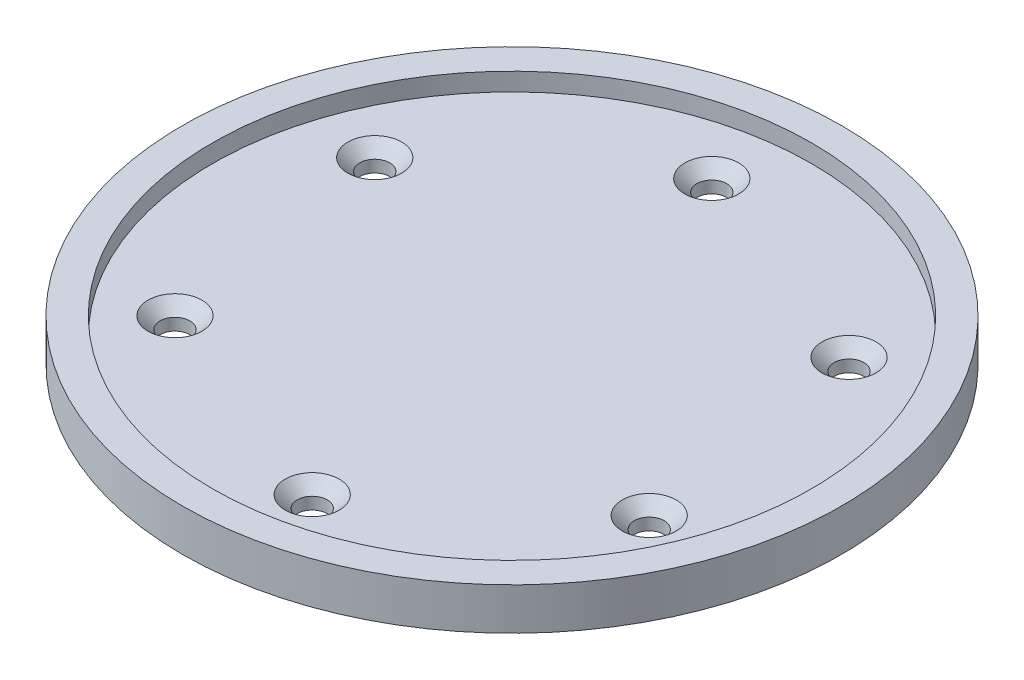
SolidWorks part; units mm, degrees
material "PBT General Purpose"
ref_plane "Front Plane" through (0, 0, 0) normal (0, 0, 1) x (1, 0, 0)
ref_plane "Top Plane" through (0, 0, 0) normal (0, 1, 0) x (1, 0, 0)
ref_plane "Right Plane" through (0, 0, 0) normal (1, 0, 0) x (0, 0, -1)
sketch "Sketch1" plane through (0, 0, 0) normal (0, 0, 1) x (1, 0, 0)
  line L0 (0, 0) -> (0, 21.4941) construction
  line L1 (50, 3.4786) -> (50, 6.4786)
  line L2 (50, 6.4786) -> (55, 6.4786)
  line L9 (50, 3.4786) -> (0, 3.4786)
  line L10 (0, -0.5214) -> (0, 3.4786)
  line L11 (0, -0.5214) -> (55, -0.5214)
  line L12 (55, -0.5214) -> (55, 6.4786)
  point P3 (55, 5.4786)
  point P7 (55, 5.4272)
  dimension "D2" = 50
  dimension "D5" = 5
  dimension "D3" = 4
  dimension "D7" = 3
revolve "Revolve1" add sketch "Sketch1" angle 360 about L0
sketch "Sketch2" plane through (0, 3.4786, 0) normal (0, 1, 0) x (1, 0, 0)
  circle A0 centre (-6.1774, 39.5201) radius 2.5
  circle A1 centre (-37.3141, 14.4103) radius 2.5
  circle A2 centre (-31.1367, -25.1098) radius 2.5
  circle A3 centre (6.1774, -39.5201) radius 2.5
  circle A4 centre (37.3141, -14.4103) radius 2.5
  circle A5 centre (31.1367, 25.1098) radius 2.5
  dimension "D1" = 5
extrude "Cut-Extrude1" cut sketch "Sketch2" against normal through all
chamfer "Chamfer1" distance 2 angle 45 6 edges at (31.1367, 3.4786, -22.6098) (37.3141, 3.4786, 16.9103) (-31.1367, 3.4786, 27.6098) (-37.3141, 3.4786, -11.9103) (-6.1774, 3.4786, -37.0201) (6.1774, 3.4786, 42.0201)
